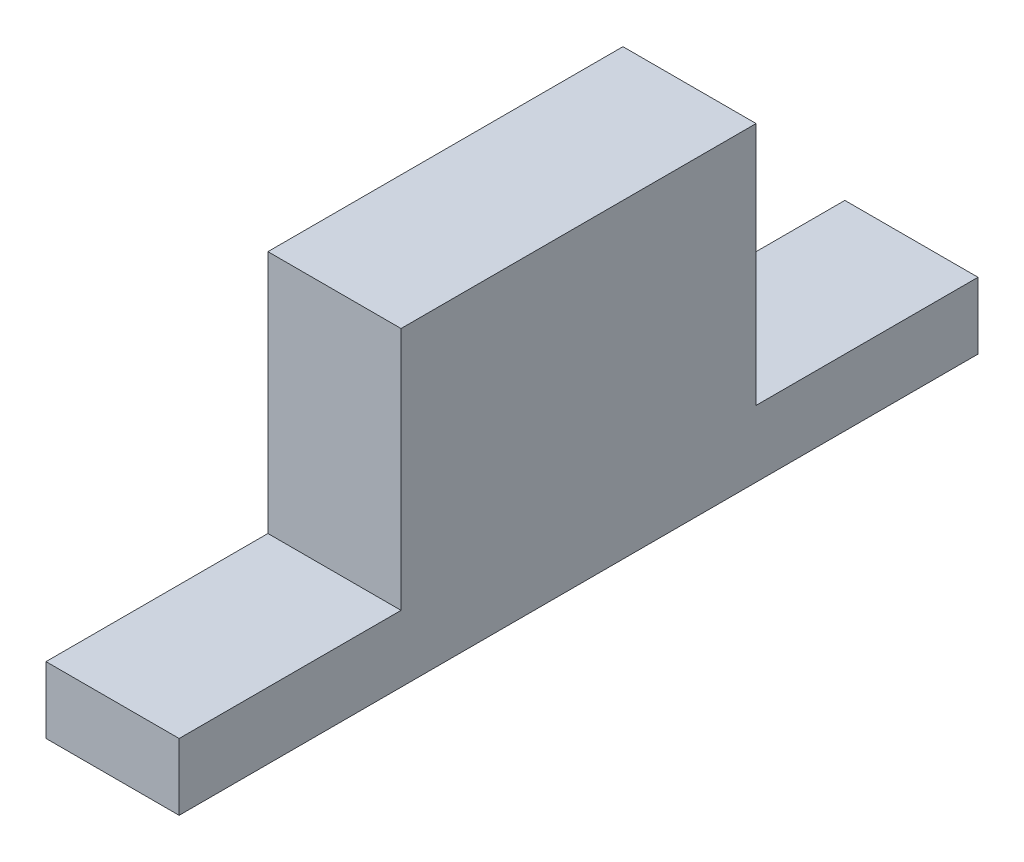
SolidWorks part; units mm, degrees
ref_plane "xy_plane" through (0, 0, 0) normal (0, 0, 1) x (1, 0, 0)
ref_plane "zx_plane" through (0, 0, 0) normal (0, 1, 0) x (1, 0, 0)
ref_plane "yz_plane" through (0, 0, 0) normal (1, 0, 0) x (0, 0, -1)
ref_axis "x_axis" through (-80.9, 0, 0) along (1, 0, 0)
ref_axis "y_axis" through (0, -50, 0) along (0, 1, 0)
ref_axis "z_axis" through (0, 0, -80.9) along (0, 0, 1)
ref_plane "xMid_plane" through (0, 0, 0) normal (1, 0, 0) x (0, 0, -1)
ref_plane "xMin_plane" through (-15, 0, 0) normal (1, 0, 0) x (0, 0, -1)
ref_plane "xMax_plane" through (15, 0, 0) normal (1, 0, 0) x (0, 0, -1)
ref_plane "yMid_plane" through (0, 0, 0) normal (0, 1, 0) x (1, 0, 0)
ref_plane "yMin_plane" through (0, -35, 0) normal (0, 1, 0) x (1, 0, 0)
ref_plane "yMax_plane" through (0, 35, 0) normal (0, 1, 0) x (1, 0, 0)
ref_plane "zMid_plane" through (0, 0, 0) normal (0, 0, 1) x (1, 0, 0)
ref_plane "zMin_plane" through (0, 0, -90) normal (0, 0, 1) x (1, 0, 0)
ref_plane "zMax_plane" through (0, 0, 90) normal (0, 0, 1) x (1, 0, 0)
sketch "projectionYz_sketch" plane through (0, 0, 0) normal (1, 0, 0) x (0, 0, -1)
  line L0 (90, -35) -> (90, -20)
  line L1 (90, -20) -> (40, -20)
  line L2 (40, -20) -> (40, 35)
  line L3 (40, 35) -> (-40, 35)
  line L4 (-40, 35) -> (-40, -20)
  line L5 (-40, -20) -> (-90, -20)
  line L6 (-90, -20) -> (-90, -35)
  line L7 (90, -35) -> (-90, -35)
  line L8 (90, 55) -> (90, -55) construction
  line L9 (55, -35) -> (-55, -35) construction
  line L10 (-90, 55) -> (-90, -55) construction
  line L11 (40, 90) -> (40, -20) construction
  line L12 (-40, 90) -> (-40, -20) construction
  line L13 (55, 35) -> (-55, 35) construction
  point P2 (85.0524, -45.3186)
  point P15 (47.4084, 0.6742)
  dimension "D1" = 15
extrude "mainBody_extrude" add sketch "projectionYz_sketch" along normal up to surface (15 mm away) from surface up to plane "xMax_plane" starting at plane "xMin_plane"
equation "\"D1@xMin_plane\"= \"externalParameters.this.extentX\" / 2"
equation "\"D1@xMax_plane\" = \"externalParameters.this.extentX\" / 2"
equation "\"D1@yMin_plane\" = \"externalParameters.this.extentY\" / 2"
equation "\"D1@yMax_plane\" = \"externalParameters.this.extentY\" / 2"
equation "\"D1@zMin_plane\" = \"externalParameters.this.extentZ\" / 2"
equation "\"D1@zMax_plane\" = \"externalParameters.this.extentZ\" / 2"
equation "\"D1@projectionYz_sketch\"=\"externalParameters.this.foot.extentY\""
